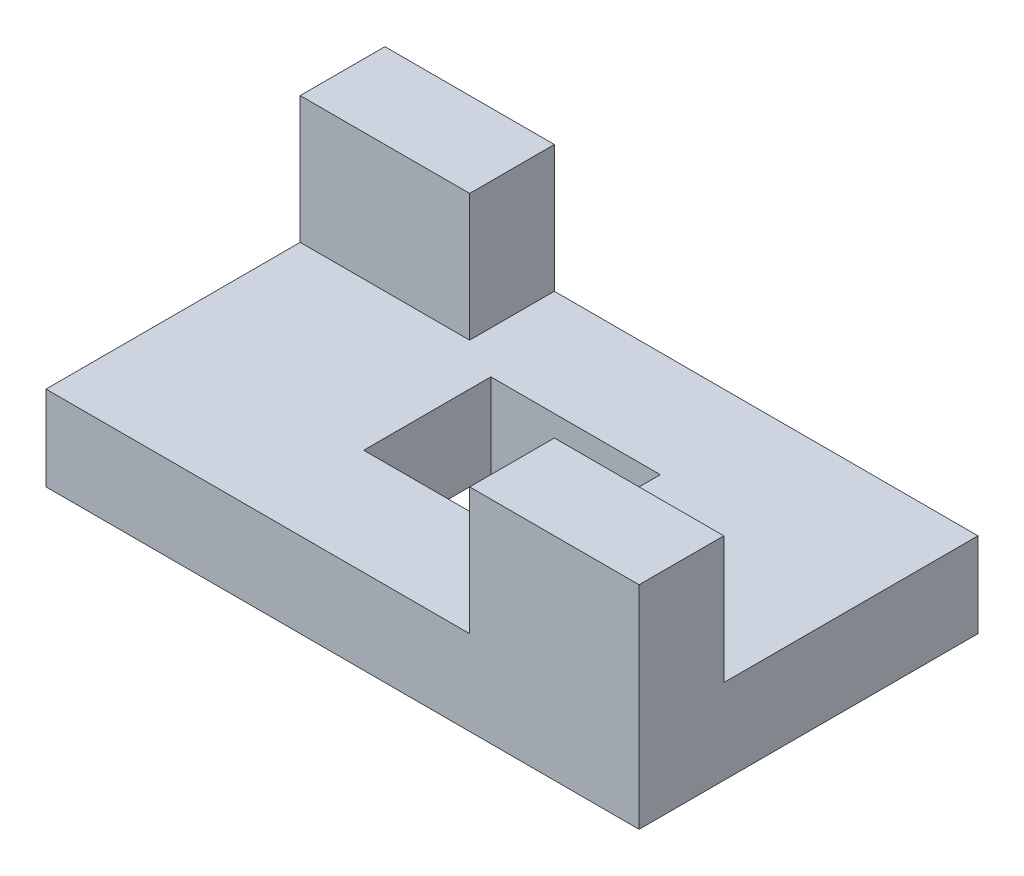
SolidWorks part; units mm, degrees
ref_plane "Front Plane" through (0, 0, 0) normal (0, 0, 1) x (1, 0, 0)
ref_plane "Top Plane" through (0, 0, 0) normal (0, 1, 0) x (1, 0, 0)
ref_plane "Right Plane" through (0, 0, 0) normal (1, 0, 0) x (0, 0, -1)
sketch "Sketch1" plane through (0, 0, 0) normal (0, 1, 0) x (1, 0, 0)
  line L1 (-28, -16) -> (28, -16)
  line L2 (-28, -16) -> (-28, 16)
  line L3 (-28, 16) -> (28, 16)
  line L4 (28, -16) -> (28, 16)
  line L5 (-28, -16) -> (28, 16) construction
  line L6 (-28, 16) -> (28, -16) construction
  line L7 (-8, -6) -> (8, -6)
  line L8 (-8, -6) -> (-8, 6)
  line L9 (-8, 6) -> (8, 6)
  line L10 (8, -6) -> (8, 6)
  line L11 (-8, -6) -> (8, 6) construction
  line L12 (-8, 6) -> (8, -6) construction
  line L13 (-28, 16) -> (-12, 16)
  line L14 (-28, 16) -> (-28, 8)
  line L15 (-28, 8) -> (-12, 8)
  line L16 (-12, 16) -> (-12, 8)
  line L17 (28, -16) -> (12, -16)
  line L18 (28, -16) -> (28, -8)
  line L19 (28, -8) -> (12, -8)
  line L20 (12, -16) -> (12, -8)
  point P0 (0, 0)
  point P5 (0, 0)
  dimension "D1" = 56
  dimension "D2" = 32
  dimension "D3" = 16
  dimension "D4" = 12
  dimension "D5" = 16
  dimension "D6" = 8
extrude "Boss-Extrude1" [suppressed] add sketch "Sketch1" along normal blind 10 contours L1 L20 L19 L4 L3 L16 L15 L2 L10 L7 L8 L9
extrude "Boss-Extrude2" add sketch "Sketch1<3>" along normal blind 8 contours L1 L20 L19 L4 L3 L16 L15 L2 L10 L7 L8 L9 region at (-27.355, 0, 4)
sketch "Sketch1<3>" plane through (0, 0, 0) normal (0, 1, 0) x (1, 0, 0) same geometry as "Sketch1"
extrude "Boss-Extrude3" add sketch "Sketch1<4>" along normal blind 20 contours L20 L1 L4 L19 | L16 L3 L2 L15 region at (20, 0, 12) region at (-20, 0, -12)
sketch "Sketch1<4>" plane through (0, 0, 0) normal (0, 1, 0) x (1, 0, 0) same geometry as "Sketch1"
